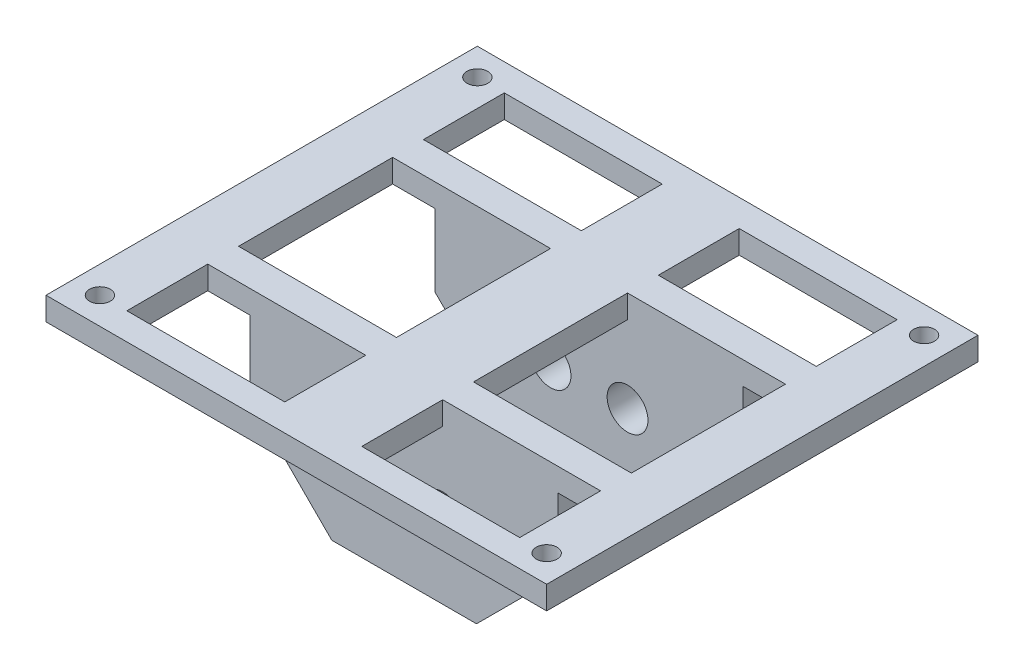
SolidWorks part; units mm, degrees
ref_plane "Front Plane" through (0, 0, 0) normal (0, 0, 1) x (1, 0, 0)
ref_plane "Top Plane" through (0, 0, 0) normal (0, 1, 0) x (1, 0, 0)
ref_plane "Right Plane" through (0, 0, 0) normal (1, 0, 0) x (0, 0, -1)
sketch "Sketch1" plane through (0, 0, 0) normal (0, 1, 0) x (1, 0, 0)
  line L0 (3.5, 52.5) -> (61.5, 52.5) construction
  line L1 (0, 0) -> (65, 0)
  line L2 (0, 0) -> (0, 56)
  line L3 (0, 56) -> (65, 56)
  line L4 (65, 0) -> (65, 56)
  line L5 (61.5, 52.5) -> (61.5, 3.5) construction
  line L6 (61.5, 3.5) -> (3.5, 3.5) construction
  line L7 (3.5, 3.5) -> (3.5, 52.5) construction
  line L14 (0, 28) -> (65, 28) construction
  line L17 (7, 38) -> (27.5, 38)
  line L18 (27.5, 38) -> (27.5, 18)
  line L19 (27.5, 18) -> (7, 18)
  line L20 (37.5, 38) -> (37.5, 18)
  line L21 (32.5, 56) -> (32.5, 0) construction
  line L22 (7, 38) -> (7, 18)
  line L23 (58, 18) -> (58, 38)
  line L24 (37.5, 38) -> (58, 38)
  line L25 (37.5, 18) -> (58, 18)
  line L27 (7, 52.5) -> (27.5, 52.5)
  line L28 (7, 52.5) -> (7, 42)
  line L29 (7, 42) -> (27.5, 42)
  line L30 (58, 52.5) -> (58, 42)
  line L34 (27.5, 42) -> (27.5, 52.5)
  line L35 (37.5, 42) -> (37.5, 52.5)
  line L36 (37.5, 42) -> (58, 42)
  line L37 (37.5, 52.5) -> (58, 52.5)
  line L38 (37.5, 3.5) -> (58, 3.5)
  line L39 (37.5, 14) -> (37.5, 3.5)
  line L40 (37.5, 14) -> (58, 14)
  line L41 (58, 3.5) -> (58, 14)
  line L42 (7, 3.5) -> (7, 14)
  line L43 (7, 14) -> (27.5, 14)
  line L44 (27.5, 14) -> (27.5, 3.5)
  line L45 (7, 3.5) -> (27.5, 3.5)
  circle A0 centre (3.5, 52.5) radius 3.5 construction
  circle A1 centre (61.5, 52.5) radius 3.5 construction
  circle A2 centre (61.5, 3.5) radius 3.5 construction
  circle A3 centre (3.5, 3.5) radius 3.5 construction
  circle A4 centre (3.5, 52.5) radius 1.35
  circle A5 centre (61.5, 52.5) radius 1.35
  circle A6 centre (61.5, 3.5) radius 1.35
  circle A7 centre (3.5, 3.5) radius 1.35
  point P18 (6, 6)
  point P19 (6, 50)
  point P20 (59, 50)
  point P21 (59, 6)
  dimension "D4" = 7
  dimension "D5" = 2.7
  dimension "D1" = 56
  dimension "D2" = 65
  dimension "D3" = 58
  dimension "D7" = 3.5
  dimension "D8" = 10
  dimension "D6" = 3.5
  dimension "D9" = 20
  dimension "D10" = 4
extrude "Boss-Extrude1" add sketch "Sketch1" along normal blind 3
sketch "Sketch5" plane through (0, 0, 0) normal (0, -1, 0) x (1, 0, 0)
  line L0 (7, -18) -> (27.5, -18) construction
  line L1 (12.5, -18) -> (52.5, -18)
  line L2 (12.5, -18) -> (12.5, -14)
  line L3 (12.5, -14) -> (52.5, -14)
  line L4 (52.5, -18) -> (52.5, -14)
  line L5 (27.5, -38) -> (7, -38) construction
  line L6 (12.5, -38) -> (52.5, -38)
  line L7 (12.5, -38) -> (12.5, -42)
  line L8 (12.5, -42) -> (52.5, -42)
  line L9 (52.5, -38) -> (52.5, -42)
  line L10 (32.5, 0) -> (32.5, -56) construction
  line L11 (0, 0) -> (65, 0) construction
  line L12 (65, -56) -> (0, -56) construction
  dimension "D1" = 4
  dimension "D2" = 4
  dimension "D3" = 40
extrude "Boss-Extrude4" add sketch "Sketch5" along normal blind 20
sketch "Sketch6" plane through (0, 0, -14) normal (0, 0, 1) x (1, 0, 0)
  line L0 (27.5, -10) -> (37.5, -10) construction
  line L1 (12.5, -10) -> (52.5, -10) construction
  line L2 (12.5, -20) -> (12.5, 0) construction
  line L3 (52.5, -20) -> (52.5, 0) construction
  line L4 (32.5, 0) -> (32.5, -20) construction
  line L5 (0, 0) -> (65, 0) construction
  line L6 (52.5, -20) -> (12.5, -20) construction
  line L21 (12.5, -9.3934) -> (12.5, -20)
  line L22 (12.5, -20) -> (23.1066, -20)
  line L23 (23.1066, -20) -> (12.5, -9.3934)
  line L24 (41.8934, -20) -> (52.5, -20)
  line L25 (52.5, -20) -> (52.5, -9.3934)
  line L26 (52.5, -9.3934) -> (41.8934, -20)
  circle A0 centre (27.5, -10) radius 2.65
  circle A1 centre (37.5, -10) radius 2.65
  dimension "D1" = 5.3
  dimension "D2" = 10
  dimension "D4" = 15
  dimension "D3" = 45
extrude "Cut-Extrude1" cut sketch "Sketch6" against normal up to surface (28 mm away) up to face at (32.5, -2.3333, -42)
